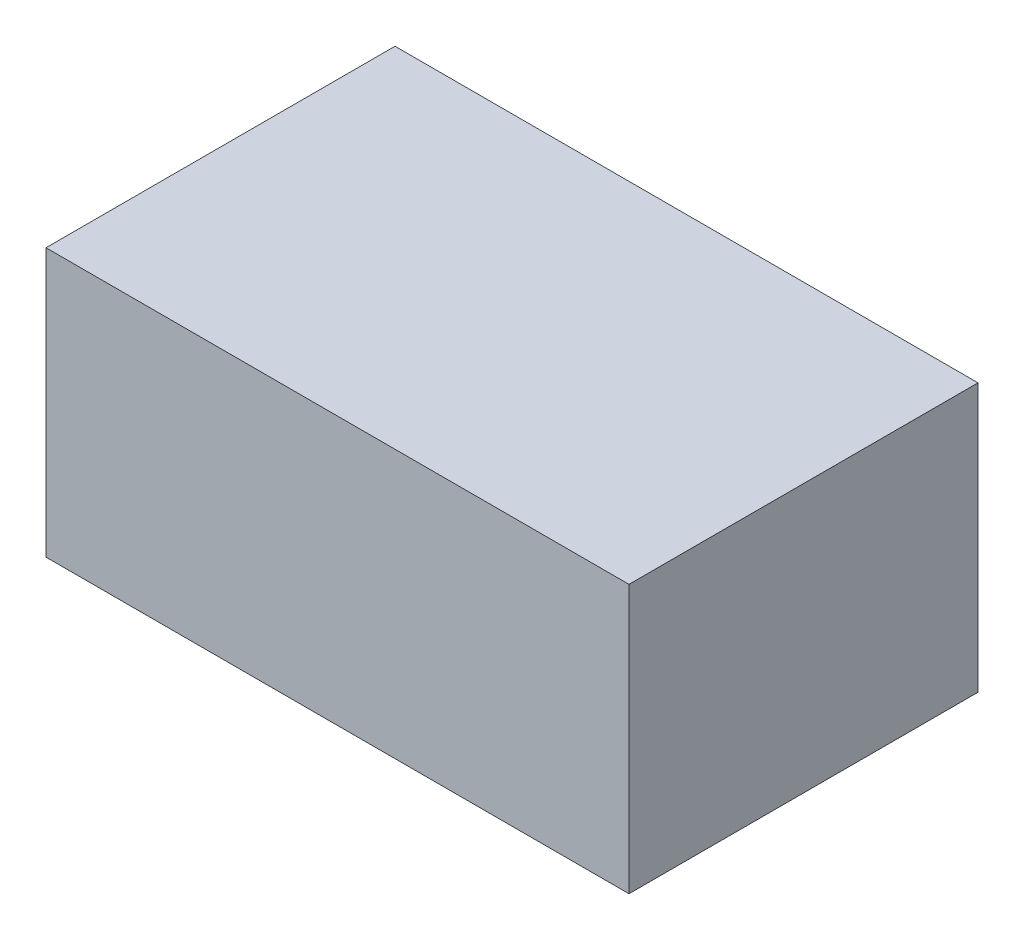
SolidWorks part; units mm, degrees
ref_plane "Front Plane" through (0, 0, 0) normal (0, 0, 1) x (1, 0, 0)
ref_plane "Top Plane" through (0, 0, 0) normal (0, 1, 0) x (1, 0, 0)
ref_plane "Right Plane" through (0, 0, 0) normal (1, 0, 0) x (0, 0, -1)
sketch "Sketch1" plane through (0, 0, 0) normal (0, 0, 1) x (1, 0, 0)
  line L1 (-22.3, -10.25) -> (22.3, -10.25)
  line L2 (-22.3, -10.25) -> (-22.3, 10.25)
  line L3 (-22.3, 10.25) -> (22.3, 10.25)
  line L4 (22.3, -10.25) -> (22.3, 10.25)
  line L5 (-22.3, -10.25) -> (22.3, 10.25) construction
  line L6 (-22.3, 10.25) -> (22.3, -10.25) construction
extrude "Envelope" add sketch "Sketch1" along normal blind 26.7
